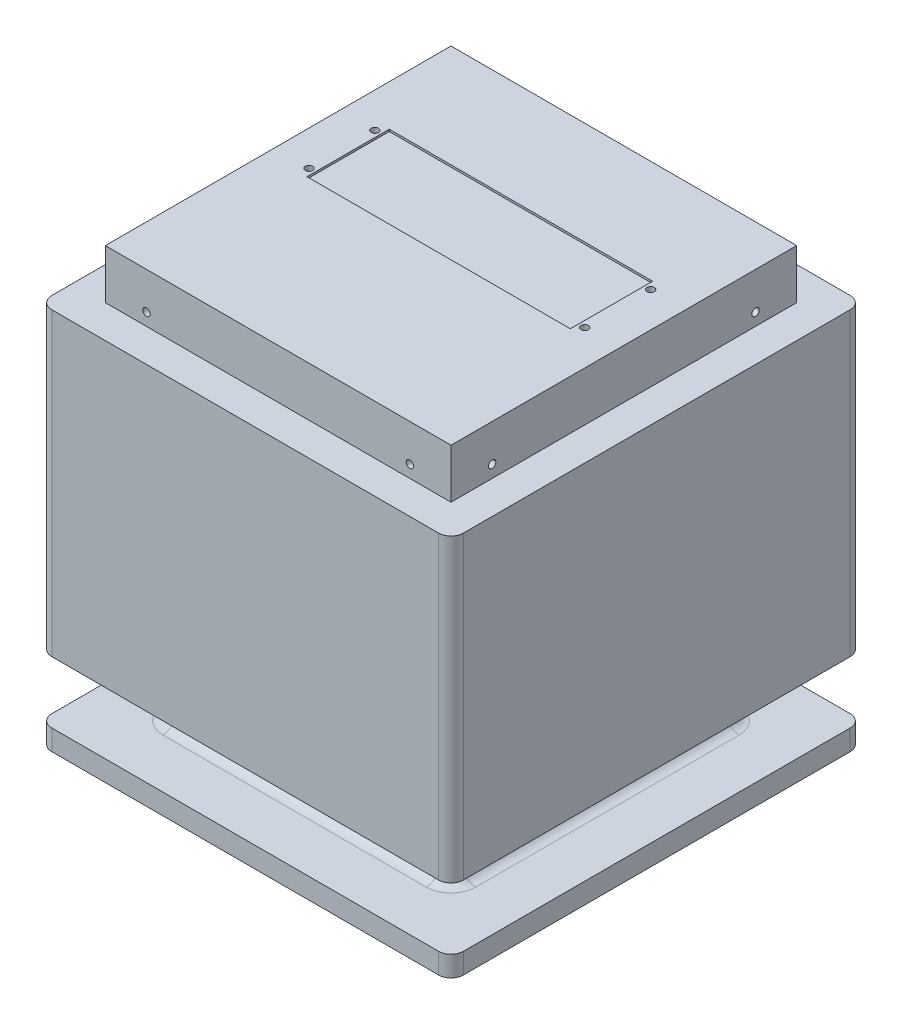
SolidWorks part; units mm, degrees
ref_plane "Front Plane" through (0, 0, 0) normal (0, 0, 1) x (1, 0, 0)
ref_plane "Top Plane" through (0, 0, 0) normal (0, 1, 0) x (1, 0, 0)
ref_plane "Right Plane" through (0, 0, 0) normal (1, 0, 0) x (0, 0, -1)
sketch "Sketch1" plane through (0, 0, 0) normal (0, 1, 0) x (1, 0, 0)
  line L1 (-50, 50) -> (50, 50)
  line L2 (-50, 50) -> (-50, -50)
  line L3 (-50, -50) -> (50, -50)
  line L4 (50, 50) -> (50, -50)
  line L5 (-50, 50) -> (50, -50) construction
  line L6 (-50, -50) -> (50, 50) construction
  point P0 (0, 0)
  dimension "D1" = 100
extrude "Boss-Extrude2" add sketch "Sketch1" along normal blind 8
sketch "Sketch2" plane through (0, 8, 0) normal (0, 1, 0) x (1, 0, 0)
  line L1 (-42, 42) -> (42, 42)
  line L2 (-42, 42) -> (-42, -42)
  line L3 (-42, -42) -> (42, -42)
  line L4 (42, 42) -> (42, -42)
  line L5 (-42, 42) -> (42, -42) construction
  line L6 (-42, -42) -> (42, 42) construction
  point P0 (0, 0)
extrude "Boss-Extrude3" add sketch "Sketch2" along normal blind 12
sketch "Sketch3" plane through (0, 20, 0) normal (0, 1, 0) x (1, 0, 0)
  line L0 (37, 37) -> (37, 32) construction
  line L1 (37, -37) -> (-37, -37)
  line L2 (37, -37) -> (37, 37)
  line L3 (37, 37) -> (-37, 37)
  line L4 (-37, -37) -> (-37, 37)
  line L5 (37, -37) -> (-37, 37) construction
  line L6 (37, 37) -> (-37, -37) construction
  line L7 (37, 32) -> (-37, 32) construction
  line L8 (-37, 32) -> (-37, 37) construction
  line L9 (37, 32) -> (37, 22) construction
  line L10 (37, 22) -> (-37, 22) construction
  line L11 (-37, 22) -> (-37, 32) construction
  line L12 (37, 22) -> (37, -8) construction
  line L13 (37, -8) -> (-37, -8) construction
  line L14 (-37, -8) -> (-37, 22) construction
  line L15 (37, -8) -> (32, -8) construction
  line L16 (32, -8) -> (32, 22) construction
  line L17 (-37, -8) -> (-32, -8) construction
  line L18 (-32, -8) -> (-32, 22) construction
  line L19 (32, -8) -> (32, -3) construction
  line L20 (32, -3) -> (-32, -3) construction
  line L21 (-32, 22) -> (-32, 17) construction
  line L22 (-32, 17) -> (32, 17) construction
  line L24 (32, -3) -> (-32, -3)
  line L25 (32, -3) -> (32, 17)
  line L26 (32, 17) -> (-32, 17)
  line L27 (-32, -3) -> (-32, 17)
  line L28 (32, 22) -> (34.5, 22) construction
  line L29 (-32, 22) -> (-34.5, 22) construction
  line L30 (34.5, -7.7713) -> (34.5, -0.7713) construction
  line L31 (34.5, 22) -> (34.5, 15) construction
  line L33 (-34.5, 22) -> (-34.5, 15) construction
  line L34 (-34.5, -8) -> (-34.5, -1) construction
  point P0 (0, 0)
extrude "Cut-Extrude1" cut sketch "Sketch3" against normal blind 0.5 contours L25 L24 L27 L26
sketch "Sketch15" plane through (0, 20, 0) normal (0, 1, 0) x (1, 0, 0)
  line L0 (32, -3) -> (37, -3) construction
  line L1 (37, -3) -> (37, 17) construction
  line L2 (37, 17) -> (32, 17) construction
  line L3 (-32, -3) -> (-37, -3) construction
  line L4 (-37, -3) -> (-37, 17) construction
  line L5 (-37, 17) -> (-32, 17) construction
  line L6 (37, -3) -> (37, -8) construction
  line L7 (-37, -3) -> (-37, -8) construction
  line L8 (-37, 17) -> (-37, 22) construction
  line L9 (37, 17) -> (37, 22) construction
  line L10 (-37, -8) -> (-33.5, -8) construction
  line L11 (37, 22) -> (33.5, 22) construction
  line L12 (37, -8) -> (33.5, -8) construction
  line L13 (-37, 22) -> (-33.5, 22) construction
  line L14 (33.5, -8) -> (33.5, -1) construction
  line L15 (33.5, 22) -> (33.5, 15) construction
  line L16 (-33.5, -8) -> (-33.5, -1) construction
  line L17 (-33.5, 22) -> (-33.5, 15) construction
sketch "Sketch17" plane through (0, 20, 0) normal (0, 1, 0) x (1, 0, 0)
  line L0 (-33.5, -8) -> (-33.5, -1) construction
  line L1 (-33.5, 22) -> (-33.5, 15) construction
hole_wizard "#2-56 Tapped Hole5" positions "3DSketch6" profile "Sketch18" tap size "#2-56" standard "ANSI Inch"
sketch3d "3DSketch6"
  point P0 (-33.5, 20, 1)
  point P3 (-33.5, 20, -15)
  point P6 (33.5, 20, -15)
  point P9 (33.5, 20, 1)
sketch "Sketch18" plane through (-33.5, 20, 1) normal (1, 0, 0) x (0, 0, 1)
  line L0 (0, 0) -> (0, 12.5342)
  line L1 (0, 12.5342) -> (0.889, 12)
  line L2 (0.889, 12) -> (0.889, 0)
  line L5 (0.889, 0) -> (0, 0)
  line L10 (0, 12.5342) -> (-0.889, 12) construction
  line L11 (0, -6.35) -> (0, 107.95) construction
  dimension "Tap Drill Dia." = 1.778
  dimension "Tap Drill Depth" = 12
  dimension "Drill Angle" = 118
cosmetic thread "Hole Thread17" parameters "D1"=10, "D2"=2.1844
cosmetic thread "Hole Thread18" parameters "D1"=10, "D2"=2.1844
cosmetic thread "Hole Thread19" parameters "D1"=10, "D2"=2.1844
cosmetic thread "Hole Thread20" parameters "D1"=10, "D2"=2.1844
sketch "Sketch20" plane through (0, 0, 42) normal (0, 0, 1) x (1, 0, 0)
  line L0 (-42, 8) -> (-42, 11) construction
  line L1 (-42, 11) -> (-32, 11) construction
  line L2 (42, 8) -> (42, 11) construction
  line L3 (42, 11) -> (32, 11) construction
sketch "Sketch21" plane through (42, 0, 0) normal (1, 0, 0) x (0, 0, -1)
  line L0 (-42, 8) -> (-42, 11) construction
  line L1 (-42, 11) -> (-32, 11) construction
  line L2 (42, 8) -> (42, 11) construction
  line L3 (42, 11) -> (32, 11) construction
sketch "Sketch22" plane through (0, 0, -42) normal (0, 0, -1) x (-1, 0, 0)
  line L0 (-42, 8) -> (-42, 11) construction
  line L1 (-42, 11) -> (-32, 11) construction
  line L2 (42, 8) -> (42, 11) construction
  line L3 (42, 20) -> (42, 8) construction
  line L4 (42, 11) -> (32, 11) construction
sketch "Sketch23" plane through (-42, 0, 0) normal (-1, 0, 0) x (0, 0, 1)
  line L0 (-42, 8) -> (-42, 11) construction
  line L1 (-42, 11) -> (-32, 11) construction
  line L2 (42, 8) -> (42, 11) construction
  line L3 (42, 11) -> (32, 11) construction
hole_wizard "#2-56 Tapped Hole6" positions "3DSketch8" profile "Sketch24" tap size "#2-56" standard "ANSI Inch"
sketch3d "3DSketch8"
  point P0 (-42, 11, -32)
  point P3 (-32, 11, -42)
  point P6 (-42, 11, 32)
  point P9 (32, 11, -42)
sketch "Sketch24" plane through (-42, 11, -32) normal (0, 1, 0) x (0, 0, 1)
  line L0 (0, 0) -> (0, 7.5342)
  line L1 (0, 7.5342) -> (0.889, 7)
  line L2 (0.889, 7) -> (0.889, 0)
  line L5 (0.889, 0) -> (0, 0)
  line L10 (0, 7.5342) -> (-0.889, 7) construction
  line L11 (0, -6.35) -> (0, 107.95) construction
  dimension "Tap Drill Dia." = 1.778
  dimension "Tap Drill Depth" = 7
  dimension "Drill Angle" = 118
cosmetic thread "Hole Thread21" parameters "D1"=7, "D2"=2.1844
cosmetic thread "Hole Thread22" parameters "D1"=7, "D2"=2.1844
cosmetic thread "Hole Thread23" parameters "D1"=7, "D2"=2.1844
cosmetic thread "Hole Thread24" parameters "D1"=7, "D2"=2.1844
hole_wizard "#2-56 Tapped Hole7" positions "3DSketch9" profile "Sketch25" tap size "#2-56" standard "ANSI Inch"
sketch3d "3DSketch9"
  point P0 (-32, 11, 42)
  point P3 (32, 11, 42)
  point P6 (42, 11, 32)
  point P9 (42, 11, -32)
sketch "Sketch25" plane through (-32, 11, 42) normal (1, 0, 0) x (0, -1, 0)
  line L0 (0, 0) -> (0, 7.5342)
  line L1 (0, 7.5342) -> (0.889, 7)
  line L2 (0.889, 7) -> (0.889, 0)
  line L5 (0.889, 0) -> (0, 0)
  line L10 (0, 7.5342) -> (-0.889, 7) construction
  line L11 (0, -6.35) -> (0, 107.95) construction
  dimension "Tap Drill Dia." = 1.778
  dimension "Tap Drill Depth" = 7
  dimension "Drill Angle" = 118
cosmetic thread "Hole Thread25" parameters "D1"=6.98, "D2"=2.1844
cosmetic thread "Hole Thread26" parameters "D1"=6.98, "D2"=2.1844
cosmetic thread "Hole Thread27" parameters "D1"=6.98, "D2"=2.1844
cosmetic thread "Hole Thread28" parameters "D1"=6.98, "D2"=2.1844
sketch "Sketch28" plane through (0, 0, 0) normal (0, -1, 0) x (-1, 0, 0)
  line L1 (50, 50) -> (-50, 50)
  line L2 (50, 50) -> (50, -50)
  line L3 (50, -50) -> (-50, -50)
  line L4 (-50, 50) -> (-50, -50)
extrude "Boss-Extrude7" add sketch "Sketch28" along normal blind 65
sketch "Sketch31" plane through (0, -65, 0) normal (0, -1, 0) x (-1, 0, 0)
  line L1 (35, -35) -> (-35, -35)
  line L2 (35, -35) -> (35, 35)
  line L3 (35, 35) -> (-35, 35)
  line L4 (-35, -35) -> (-35, 35)
  line L5 (35, -35) -> (-35, 35) construction
  line L6 (35, 35) -> (-35, -35) construction
  point P0 (0, 0)
extrude "Boss-Extrude8" add sketch "Sketch31" along normal blind 15
sketch "Sketch32" plane through (0, -80, 0) normal (0, -1, 0) x (-1, 0, 0)
  line L1 (50, -50) -> (-50, -50)
  line L2 (50, -50) -> (50, 50)
  line L3 (50, 50) -> (-50, 50)
  line L4 (-50, -50) -> (-50, 50)
  line L5 (50, -50) -> (-50, 50) construction
  line L6 (50, 50) -> (-50, -50) construction
  point P0 (0, 0)
extrude "Boss-Extrude9" add sketch "Sketch32" along normal blind 5
fillet "Fillet1" radius 3 3 edges at (50, -28.5, -50) (-50, -28.5, 50) (-50, -28.5, -50)
fillet "Fillet2" radius 3 7 edges at (-35, -72.5, 35) (-50, -82.5, 50) (50, -82.5, -50) (50, -82.5, 50) (35, -72.5, -35) (35, -72.5, 35) (50, -28.5, 50)
fillet "Fillet3" radius 3 2 edges at (-50, -82.5, -50) (-35, -72.5, -35)
fillet "Fillet4" radius 3 8 edges at (-34.1213, -80, -34.1213) (-35, -80, 0) (-34.1213, -80, 34.1213) (0, -80, 35) (34.1213, -80, 34.1213) (35, -80, 0) (34.1213, -80, -34.1213) (0, -80, -35)
fillet "Fillet5" radius 3 8 edges at (-34.1213, -65, -34.1213) (-35, -65, 0) (-34.1213, -65, 34.1213) (0, -65, 35) (34.1213, -65, 34.1213) (35, -65, 0) (34.1213, -65, -34.1213) (0, -65, -35)
sketch "Sketch35" plane through (0, -85, 0) normal (0, -1, 0) x (-1, 0, 0)
  text T0 "HUAN Q. BUI\r\nAUGUST 2021\r\nMIT, BOSTON, MA" font "Comic Sans MS" height in points 8
extrude "Cut-Extrude3" cut sketch "Sketch35" against normal blind 1
